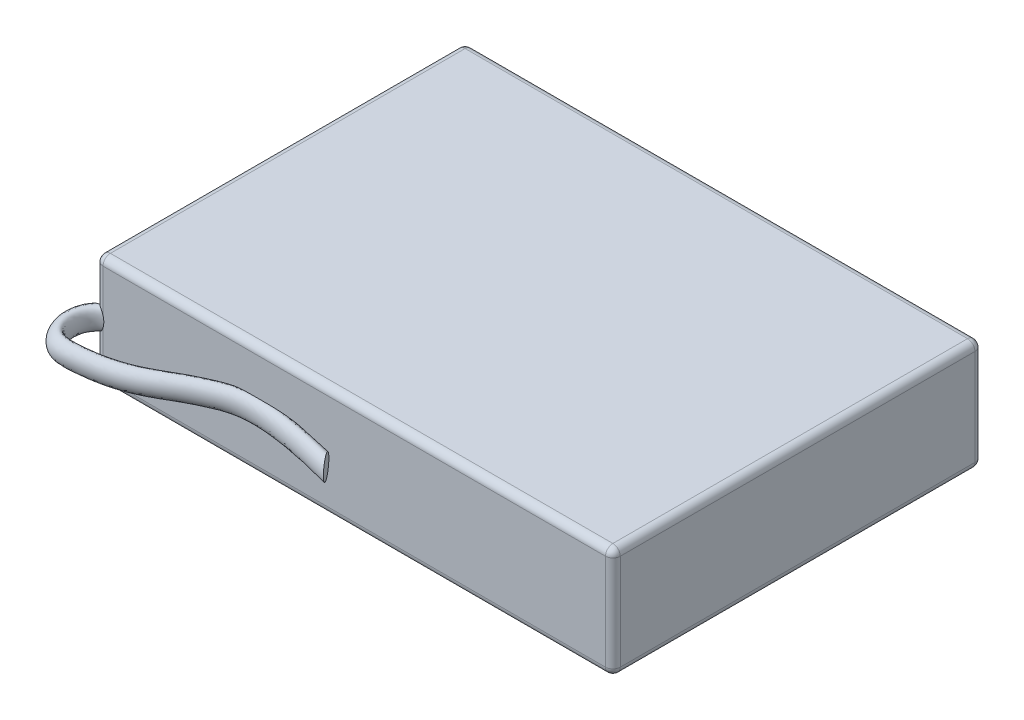
SolidWorks part; units mm, degrees
material "PE(聚乙烯)"
ref_plane "前视基准面" through (0, 0, 0) normal (0, 0, 1) x (1, 0, 0)
ref_plane "上视基准面" through (0, 0, 0) normal (0, 1, 0) x (1, 0, 0)
ref_plane "右视基准面" through (0, 0, 0) normal (1, 0, 0) x (0, 0, -1)
other "Configuration Table"
sketch "草图1" plane through (0, 0, 0) normal (0, 1, 0) x (1, 0, 0)
  line L1 (-35, 25) -> (35, 25)
  line L2 (-35, 25) -> (-35, -25)
  line L3 (-35, -25) -> (35, -25)
  line L4 (35, 25) -> (35, -25)
  line L5 (-35, 25) -> (35, -25) construction
  line L6 (-35, -25) -> (35, 25) construction
  point P0 (0, 0)
  dimension "D1" = 70
  dimension "D2" = 50
extrude "凸台-拉伸1" add sketch "草图1" along normal blind 15
fillet "圆角1" radius 1 12 edges at (0, 15, -25) (35, 15, 0) (35, 7.5, -25) (0, 15, 25) (35, 7.5, 25) (-35, 7.5, -25) (-35, 15, 0) (-35, 7.5, 25) (0, 0, -25) (-35, 0, 0) (0, 0, 25) (35, 0, 0)
ref_plane "基准面1" through (0, 7.5, 0) normal (0, 1, 0) x (1, 0, 0)
sketch "草图2" plane through (0, 7.5, 0) normal (0, 1, 0) x (1, 0, 0)
  line L0 (34, -25) -> (-34, -25) construction
  arc A0 (-35, -24) -> (-34, -25) centre (-34, -24) ccw construction
  spline S0 degree 3 poles (-34.7071, -24.7071) (-36.678, -26.3982) (-35.7614, -31.2485) (-26.1931, -31.0207) (-22.7994, -28.3325) (-16.219, -25.1883) (-12.8207, -24.1356) (-1.8526, -26.9517) knots 0 0 0 0 0.134592 0.194668 0.555639 0.640684 1 1 1 1
  dimension "D1" = 6
ref_plane "基准面2" through (0, 0, 24.7071) normal (0, 0, 1) x (1, 0, 0)
sketch "草图4" plane through (0, 0, 24.7071) normal (0, 0, 1) x (1, 0, 0)
  circle A0 centre (-34.7071, 7.5) radius 1.5
  dimension "D1" = 3
sweep "扫描1" add profiles "草图4" path "草图2"
